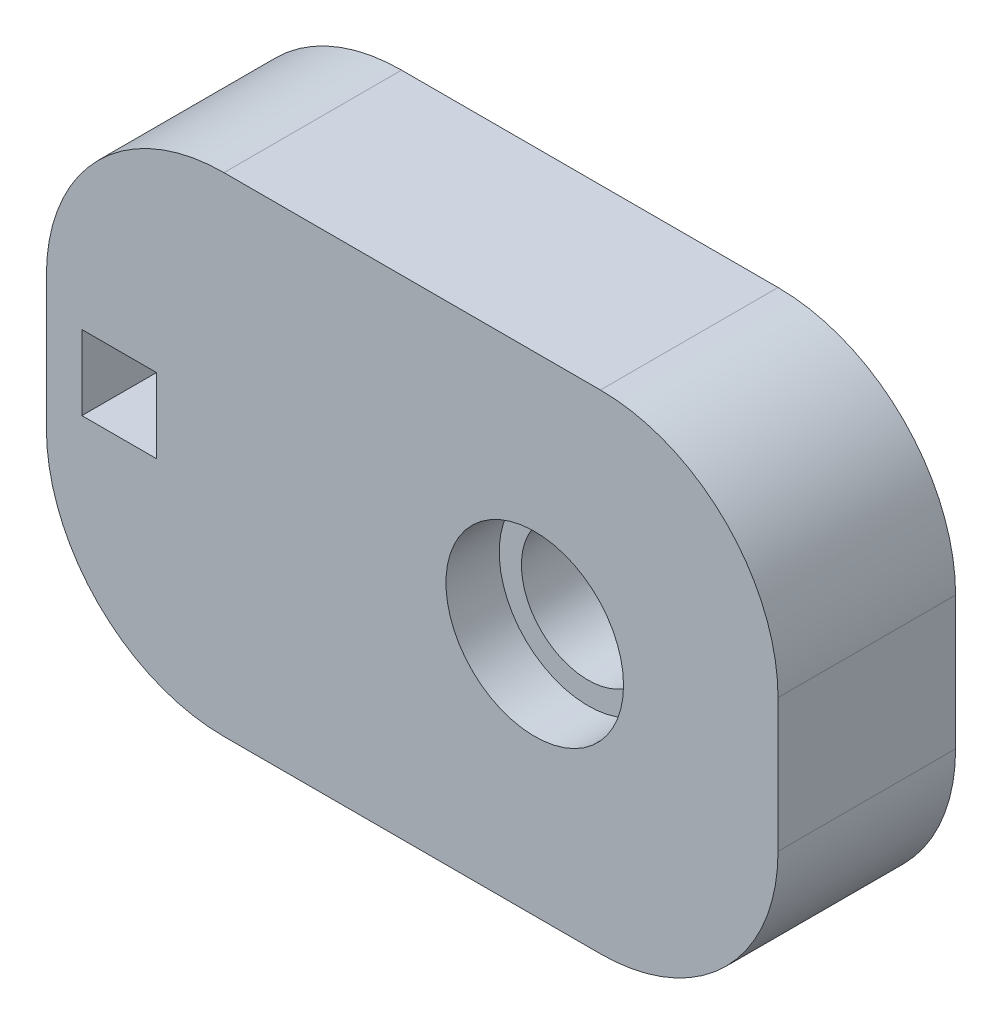
SolidWorks part; units mm, degrees
ref_plane "Front Plane" through (0, 0, 0) normal (0, 0, 1) x (1, 0, 0)
ref_plane "Top Plane" through (0, 0, 0) normal (0, 1, 0) x (1, 0, 0)
ref_plane "Right Plane" through (0, 0, 0) normal (1, 0, 0) x (0, 0, -1)
sketch "Sketch1" plane through (0, 0, 0) normal (0, 0, 1) x (1, 0, 0)
  line L0 (254.5643, -88.6707) -> (254.5643, -134.0707) construction
  line L1 (213.3643, -97.6207) -> (254.5643, -97.6207)
  line L2 (213.3643, -97.6207) -> (213.3643, -125.1207)
  line L3 (213.3643, -125.1207) -> (254.5643, -125.1207)
  line L4 (254.5643, -97.6207) -> (254.5643, -125.1207)
  line L5 (254.5643, -111.3707) -> (227.1643, -111.3707) construction
  line L6 (227.1643, -134.0707) -> (227.1643, -88.6707) construction
  line L7 (213.3643, -103.7735) -> (213.3643, -118.9679) construction
  line L8 (213.3643, -103.7735) -> (213.3643, -118.9679)
  point P0 (0, -31.3739)
  point P5 (254.5643, -111.3707)
  dimension "D2" = 27.5
extrude "Boss-Extrude1" add sketch "Sketch1" along normal blind 10 contours L2 L3 L4 L1
sketch "Sketch2" plane through (0, 0, 10) normal (0, 0, 1) x (1, 0, 0)
  line L0 (227.1643, -88.6707) -> (254.5643, -88.6707) construction
  line L3 (227.1643, -88.6707) -> (254.5643, -88.6707) construction
  line L4 (227.1643, -134.0707) -> (227.1643, -88.6707) construction
  line L6 (254.5643, -111.3707) -> (227.1643, -111.3707) construction
  line L7 (254.5643, -97.6207) -> (254.5643, -125.1207) construction
  line L8 (227.1643, -134.0707) -> (227.1643, -88.6707) construction
  circle A0 centre (240.8643, -111.3707) radius 5
  dimension "D1" = 10
extrude "Cut-Extrude1" cut sketch "Sketch2" against normal blind 3
sketch "Sketch3" plane through (0, 0, 10) normal (0, 0, 1) x (1, 0, 0)
  line L15 (254.5643, -111.3707) -> (149.3689, -111.3707) construction
  line L16 (254.5643, -97.6207) -> (254.5643, -125.1207) construction
  line L17 (213.3643, -97.6207) -> (213.3643, -125.1207) construction
  line L19 (219.5643, -109.2707) -> (215.3643, -109.2707)
  line L20 (219.5643, -113.4707) -> (219.5643, -109.2707)
  line L21 (215.3643, -113.4707) -> (219.5643, -113.4707)
  line L22 (215.3643, -109.2707) -> (215.3643, -113.4707)
  point P7 (215.3643, -111.3707)
  dimension "D1" = 4.2
  dimension "D2" = 2
extrude "Cut-Extrude2" cut sketch "Sketch3" against normal blind 5
sketch "Sketch4" plane through (0, 0, 10) normal (0, 0, 1) x (1, 0, 0)
  circle A0 centre (240.8643, -111.3707) radius 3.75
  dimension "D1" = 7.5
extrude "Cut-Extrude3" cut sketch "Sketch4" against normal offset from surface (7.5 mm away) 2.5 up to face at (233.9643, -111.3707, 0)
fillet "Fillet1" radius 10 4 edges at (254.5643, -125.1207, 5) (254.5643, -97.6207, 5) (213.3643, -125.1207, 5) (213.3643, -97.6207, 5)
